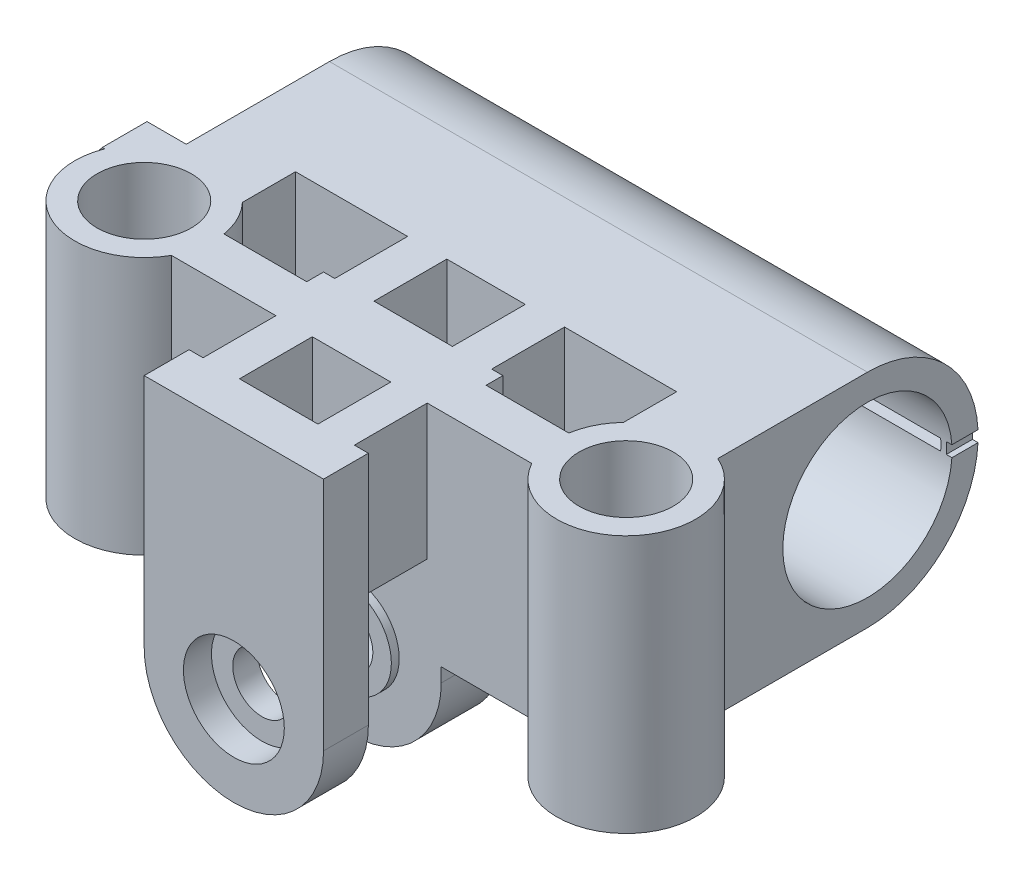
SolidWorks part; units mm, degrees
material "ABS"
ref_plane "Front Plane" through (0, 0, 0) normal (0, 0, 1) x (1, 0, 0)
ref_plane "Top Plane" through (0, 0, 0) normal (0, 1, 0) x (1, 0, 0)
ref_plane "Right Plane" through (0, 0, 0) normal (1, 0, 0) x (0, 0, -1)
sketch "Sketch1" plane through (0, 0, 0) normal (0, 1, 0) x (1, 0, 0)
  line L0 (-24, 0) -> (24, 0)
  line L1 (24, 0) -> (24, -23.2264)
  line L2 (16.0741, -31.9) -> (6.75, -31.9)
  line L3 (6.75, -31.9) -> (6.75, -38.4)
  line L4 (6.75, -38.4) -> (8, -38.4)
  line L5 (8, -38.4) -> (8, -42.4)
  line L6 (8, -42.4) -> (-8, -42.4)
  line L7 (-8, -42.4) -> (-8, -38.4)
  line L8 (-8, -38.4) -> (-6.75, -38.4)
  line L9 (-6.75, -38.4) -> (-6.75, -31.9)
  line L10 (-6.75, -31.9) -> (-16.0741, -31.9)
  line L11 (-24, -23.2264) -> (-24, 0)
  line L12 (-24, 0) -> (-24.1658, 0.0829)
  arc A0 (-24, -23.2264) -> (-16.0741, -31.9) centre (-21.5, -28.9) ccw
  arc A1 (16.0741, -31.9) -> (24, -23.2264) centre (21.5, -28.9) ccw
  dimension "D4" = 12.4
  dimension "D5" = 13.5
  dimension "D6" = 13.5
  dimension "D1" = 16
  dimension "D2" = 4
  dimension "D3" = 6.5
  dimension "D8" = 48
  dimension "D9" = 42.4
  dimension "D10" = 13.5
extrude "Boss-Extrude1" add sketch "Sketch1" along normal blind 19.75 contours L2 A1 L1 L0 L11 A0 L10 L9 L8 L7 L6 L5 L4 L3 region at (0, 0, 18.5988)
fillet "Fillet1" 2 edges at (0, 19.75, 0) (0, 0, 0) type full round first side face at (0, 19.75, 30.2494) second side face at (0, 0, 30.2494) middle face at (0, 9.875, 0)
sketch "Sketch2" plane through (24, 0, 0) normal (1, 0, 0) x (0, 0, -1)
  circle A0 centre (-9.875, 9.875) radius 7.55
  dimension "D1" = 15.1
extrude "Cut-Extrude1" cut sketch "Sketch2" against normal through all
sketch "Sketch3" plane through (0, 19.75, 0) normal (0, 1, 0) x (1, 0, 0)
  circle A0 centre (21.5, -28.9) radius 6.2
  arc A1 (16.0741, -31.9) -> (24, -23.2264) centre (21.5, -28.9) ccw construction
  circle A2 centre (-21.5, -28.9) radius 6.2
  arc A3 (-24, -23.2264) -> (-16.0741, -31.9) centre (-21.5, -28.9) ccw construction
extrude "Boss-Extrude2" add sketch "Sketch3" against normal blind 23
sketch "Sketch4" plane through (0, 19.75, 0) normal (0, 1, 0) x (1, 0, 0)
  circle A0 centre (-21.5, -28.9) radius 4.2
  circle A1 centre (21.5, -28.9) radius 4.2
  dimension "D1" = 8.4
extrude "Cut-Extrude2" cut sketch "Sketch4" against normal through all
sketch "Sketch5" plane through (0, 19.75, 0) normal (0, 1, 0) x (1, 0, 0)
  line L0 (0, -38.4) -> (0, -42.4) construction
  line L1 (-3.5, -19.9) -> (3.5, -19.9)
  line L2 (-3.5, -19.9) -> (-3.5, -26.4)
  line L3 (-3.5, -26.4) -> (3.5, -26.4)
  line L4 (3.5, -19.9) -> (3.5, -26.4)
  line L5 (-3.5, -31.9) -> (3.5, -31.9)
  line L6 (-3.5, -31.9) -> (-3.5, -38.4)
  line L7 (-3.5, -38.4) -> (3.5, -38.4)
  line L8 (3.5, -31.9) -> (3.5, -38.4)
  line L9 (17, -19.9) -> (7, -19.9)
  line L10 (17, -19.9) -> (17, -24.635)
  line L11 (15.3812, -27.9) -> (8, -27.9)
  line L12 (7, -19.9) -> (7, -26.4)
  line L13 (-7, -19.9) -> (-17, -19.9)
  line L14 (-7, -19.9) -> (-7, -26.4)
  line L15 (-8, -27.9) -> (-15.3812, -27.9)
  line L16 (-17, -19.9) -> (-17, -24.635)
  line L17 (8, -42.4) -> (-8, -42.4) construction
  line L18 (-8, -27.9) -> (-8, -26.4)
  line L19 (-8, -26.4) -> (-7, -26.4)
  line L20 (7, -26.4) -> (8, -26.4)
  line L21 (8, -26.4) -> (8, -27.9)
  arc A0 (17, -24.635) -> (15.3812, -27.9) centre (21.5, -28.9) ccw
  arc A1 (-15.3812, -27.9) -> (-17, -24.635) centre (-21.5, -28.9) ccw
  dimension "D1" = 6.5
  dimension "D2" = 7
  dimension "D3" = 4
  dimension "D4" = 5.5
  dimension "D5" = 3.5
  dimension "D6" = 3.5
  dimension "D7" = 10
  dimension "D8" = 8
  dimension "D9" = 16
  dimension "D10" = 1.5
extrude "Cut-Extrude3" cut sketch "Sketch5" against normal through all
sketch "Sketch6" plane through (0, 0, 42.4) normal (0, 0, 1) x (1, 0, 0)
  line L0 (-8, 0) -> (-8, -1.25)
  line L1 (8, -1.25) -> (8, 0)
  line L2 (8, 19.75) -> (-8, 19.75) construction
  line L7 (-8, 0) -> (8, 0)
  line L8 (8, 0) -> (8, 19.75)
  line L9 (8, 19.75) -> (-8, 19.75)
  line L10 (-8, 19.75) -> (-8, 0)
  line L11 (-8, 0) -> (8, 0)
  arc A0 (-8, -1.25) -> (8, -1.25) centre (0, -1.25) ccw
  dimension "D1" = 29
  dimension "D2" = 0
extrude "Boss-Extrude3" add sketch "Sketch6" against normal blind 4
sketch "Sketch7" plane through (6.75, 0, 0) normal (1, 0, 0) x (0, 0, -1)
  line L0 (-38.4, 19.75) -> (-38.4, 0) construction
  line L1 (-31.9, 0) -> (-38.4, 0)
  line L2 (-31.9, 0) -> (-31.9, 7.7)
  line L3 (-31.9, 7.7) -> (-38.4, 7.7)
  line L4 (-38.4, 0) -> (-38.4, 7.7)
  line L5 (-31.9, 19.75) -> (-38.4, 19.75) construction
  dimension "D1" = 12.05
extrude "Cut-Extrude4" cut sketch "Sketch7" against normal up to surface (13.5 mm away) up to face at (-6.75, 9.875, 35.15)
sketch "Sketch8" plane through (0, 0, 31.9) normal (0, 0, 1) x (1, 0, 0)
  line L0 (-8, -1.25) -> (-8, 0)
  line L1 (-8, 19.75) -> (-8, -1.25) construction
  line L2 (16.0741, 0) -> (-16.0741, 0) construction
  line L3 (-8, 0) -> (8, 0)
  line L4 (8, 19.75) -> (8, -1.25) construction
  line L5 (8, 0) -> (8, -1.25)
  arc A0 (-8, -1.25) -> (8, -1.25) centre (0, -1.25) ccw construction
  arc A1 (-8, -1.25) -> (8, -1.25) centre (0, -1.25) ccw
extrude "Boss-Extrude4" add sketch "Sketch8" against normal blind 5.5
sketch "Sketch9" plane through (7, 0, 0) normal (1, 0, 0) x (0, 0, -1)
  line L0 (-26.4, 0) -> (-26.4, 19.75) construction
  line L1 (-19.9, 0) -> (-26.4, 0)
  line L2 (-19.9, 0) -> (-19.9, 7.7)
  line L3 (-19.9, 7.7) -> (-26.4, 7.7)
  line L4 (-26.4, 0) -> (-26.4, 7.7)
  line L5 (-31.9, 7.7) -> (-38.4, 7.7) construction
extrude "Cut-Extrude5" cut sketch "Sketch9" against normal up to surface (14 mm away) up to face at (-7, 9.875, 23.15)
sketch "Sketch10" plane through (0, 0, 19.9) normal (0, 0, 1) x (1, 0, 0)
  line L0 (-8, -1.25) -> (-8, 0)
  line L2 (-8, 0) -> (-16.0741, 0) construction
  line L3 (-8, 0) -> (8, 0)
  line L4 (8, 0) -> (8, -1.25)
  arc A0 (-8, -1.25) -> (8, -1.25) centre (0, -1.25) ccw construction
  arc A1 (-8, -1.25) -> (8, -1.25) centre (0, -1.25) ccw
extrude "Boss-Extrude5" add sketch "Sketch10" against normal blind 4
sketch "Sketch11" plane through (0, 0, 38.4) normal (0, 0, -1) x (-1, 0, 0)
  circle A0 centre (0, -1.25) radius 4.25
  dimension "D1" = 8.5
extrude "Boss-Extrude6" add sketch "Sketch11" along normal up to surface (18.5 mm away) up to face at (0, 8.675, 19.9)
sketch "Sketch13" plane through (0, 0, 0) normal (0, -1, 0) x (1, 0, 0)
  line L0 (-4.25, 38.4) -> (-4.25, 31.9) construction
  line L1 (-4.25, 37.7) -> (4.25, 37.7)
  line L2 (-4.25, 37.7) -> (-4.25, 32.6)
  line L3 (-4.25, 32.6) -> (4.25, 32.6)
  line L4 (4.25, 37.7) -> (4.25, 32.6)
  line L5 (4.25, 31.9) -> (4.25, 38.4) construction
  line L6 (-4.25, 26.4) -> (-4.25, 19.9) construction
  line L7 (-4.25, 25.7) -> (4.25, 25.7)
  line L8 (-4.25, 25.7) -> (-4.25, 20.6)
  line L9 (-4.25, 20.6) -> (4.25, 20.6)
  line L10 (4.25, 25.7) -> (4.25, 20.6)
  line L11 (4.25, 19.9) -> (4.25, 26.4) construction
  line L12 (-8, 38.4) -> (8, 38.4) construction
  line L13 (8, 31.9) -> (-8, 31.9) construction
  line L14 (-4.25, 26.4) -> (4.25, 26.4) construction
  line L15 (8, 19.9) -> (-8, 19.9) construction
  dimension "D1" = 0.7
  dimension "D2" = 0.7
  dimension "D3" = 0.7
  dimension "D4" = 0.7
extrude "Cut-Extrude7" cut sketch "Sketch13" against normal blind 5 and the other way through all
sketch "Sketch15" plane through (0, 0, 0) normal (1, 0, 0) x (0, 0, -1)
  line L0 (-15.9, 0) -> (-15.9, 2.051)
  line L1 (-15.9, 0) -> (-9.875, 0)
  arc A1 (-15.9, 2.051) -> (-9.875, 0) centre (-9.875, 9.875) ccw
extrude "Cut-Extrude8" cut sketch "Sketch15" against normal mid plane 5
sketch "Sketch12" plane through (0, 0, 42.4) normal (0, 0, 1) x (1, 0, 0)
  circle A0 centre (0, -1.25) radius 2.6
  dimension "D1" = 5.2
extrude "Cut-Extrude6" cut sketch "Sketch12" against normal up to surface (26.5 mm away) up to face at (0, -0.7998, 15.9)
sketch "Sketch16" plane through (0, 0, 15.9) normal (0, 0, -1) x (-1, 0, 0)
  line L0 (-2.2798, 0) -> (-2.5, 0)
  line L3 (-2.5, 0) -> (-2.5, 1.8002)
  line L4 (-2.5, 1.8002) -> (2.5, 1.8002)
  line L5 (2.2798, 0) -> (2.5, 0)
  line L6 (-2.5, 0) -> (2.5, 0) construction
  line L7 (2.5, 0) -> (2.5, 1.8002)
  circle A0 centre (0, -1.25) radius 2.6 construction
  arc A1 (2.2798, 0) -> (-2.2798, 0) centre (0, -1.25) ccw
extrude "Boss-Extrude7" add sketch "Sketch16" along normal up to next
sketch "Sketch17" plane through (-24, 0, 0) normal (-1, 0, 0) x (0, 0, 1)
  line L0 (9.875, 9.875) -> (2.3416, 9.875) construction
  line L1 (2.3416, 10.375) -> (0, 10.375)
  line L2 (2.3416, 10.375) -> (2.3416, 9.375)
  line L3 (2.3416, 9.375) -> (0, 9.375)
  line L4 (0, 10.375) -> (0, 9.375)
  circle A0 centre (9.875, 9.875) radius 7.55 construction
  arc A1 (9.875, 19.75) -> (9.875, 0) centre (9.875, 9.875) ccw construction
  dimension "D1" = 1
extrude "Cut-Extrude9" cut sketch "Sketch17" against normal through all
sketch "Sketch18" plane through (-24, 0, 0) normal (-1, 0, 0) x (0, 0, 1)
  line L0 (0.0127, 10.375) -> (2.3416, 10.375)
  line L1 (2.3416, 9.375) -> (0.0127, 9.375)
  arc A0 (0.0127, 10.375) -> (0.0127, 9.375) centre (9.875, 9.875) ccw
  arc A1 (2.3416, 10.375) -> (2.3416, 9.375) centre (9.875, 9.875) ccw
extrude "Boss-Extrude8" add sketch "Sketch18" against normal blind 0.5 from offset 0.5 offset against normal yes
pattern_linear "LPattern1" count 7 spacing 7.75 along (1, 0, 0) of "Boss-Extrude8"
sketch "Sketch19" plane through (0, 0, 42.4) normal (0, 0, 1) x (1, 0, 0)
  circle A0 centre (0, -1.25) radius 4.5
  dimension "D1" = 9
extrude "Cut-Extrude10" cut sketch "Sketch19" against normal blind 2.5
sketch "Sketch20" plane through (-24, 0, 0) normal (-1, 0, 0) x (0, 0, 1)
  line L1 (22.65, 4.25) -> (26.65, 4.25)
  line L2 (22.65, 4.25) -> (22.65, 19.75)
  line L3 (22.65, 19.75) -> (26.65, 19.75)
  line L4 (26.65, 4.25) -> (26.65, 19.75)
  line L5 (23.2264, 19.75) -> (9.875, 19.75) construction
  line L6 (19.9, -9.25) -> (19.9, -1.25) construction
  dimension "D1" = 4
  dimension "D2" = 15.5
  dimension "D3" = 2.75
extrude "Boss-Extrude9" add sketch "Sketch20" along normal blind 6.45
sketch "Sketch21" plane through (0, 0, 22.65) normal (0, 0, -1) x (-1, 0, 0)
  line L0 (27.4983, 19.75) -> (30.45, 19.75)
  line L1 (30.45, 19.75) -> (30.45, 15.9032)
  line L2 (30.45, 19.75) -> (30.45, 4.25) construction
  line L3 (30.45, 15.9032) -> (27.4983, 19.75)
  dimension "D1" = 2.9517
  dimension "D2" = 3.8468
extrude "Cut-Extrude11" cut sketch "Sketch21" against normal up to next
sketch "Sketch22" plane through (0, 19.75, 0) normal (0, 1, 0) x (1, 0, 0)
  circle A0 centre (-21.5, -28.9) radius 4.2
  arc A1 (-25.0465, -26.65) -> (-24, -25.5251) centre (-21.5, -28.9) ccw construction
extrude "Cut-Extrude12" cut sketch "Sketch22" against normal through all
